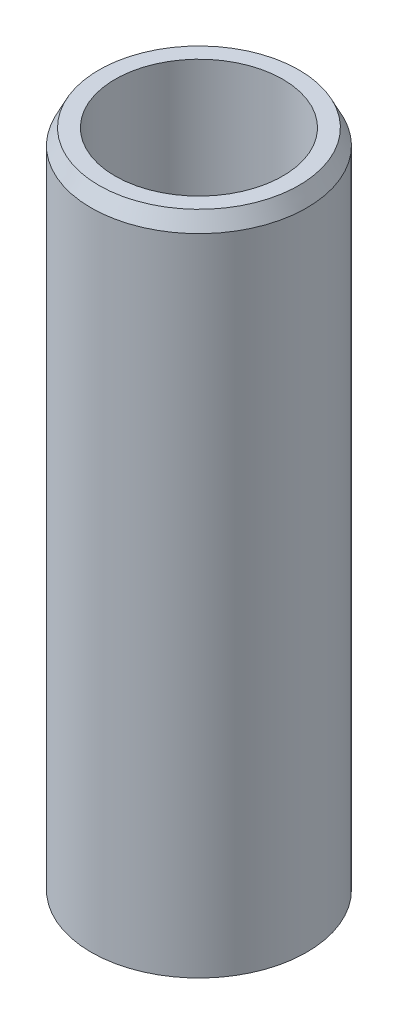
SolidWorks part; units mm, degrees
ref_plane "Front Plane" through (0, 0, 0) normal (0, 0, 1) x (1, 0, 0)
ref_plane "Top Plane" through (0, 0, 0) normal (0, 1, 0) x (1, 0, 0)
ref_plane "Right Plane" through (0, 0, 0) normal (1, 0, 0) x (0, 0, -1)
sketch "Sketch1" plane through (0, 0, 0) normal (0, 1, 0) x (1, 0, 0)
  circle A0 centre (0, 0) radius 32.5
  dimension "SHAFT_OD" = 65
extrude "Boss-Extrude1" add sketch "Sketch1" along normal blind 201.3072
sketch "Sketch2" plane through (0, 0, 0) normal (0, 1, 0) x (1, 0, 0)
  circle A0 centre (0, 0) radius 25.2721
  dimension "BORE_D" = 50.5442
extrude "Cut-Extrude1" cut sketch "Sketch2" along normal through all
chamfer "Chamfer1" distance 4.6861 angle 26.657 2 edges at (0, 201.3072, 32.5) (0, 0, 32.5) first distance on face at (0, 201.3072, 32.5) first distance on face at (0, 0, 25.2721)
